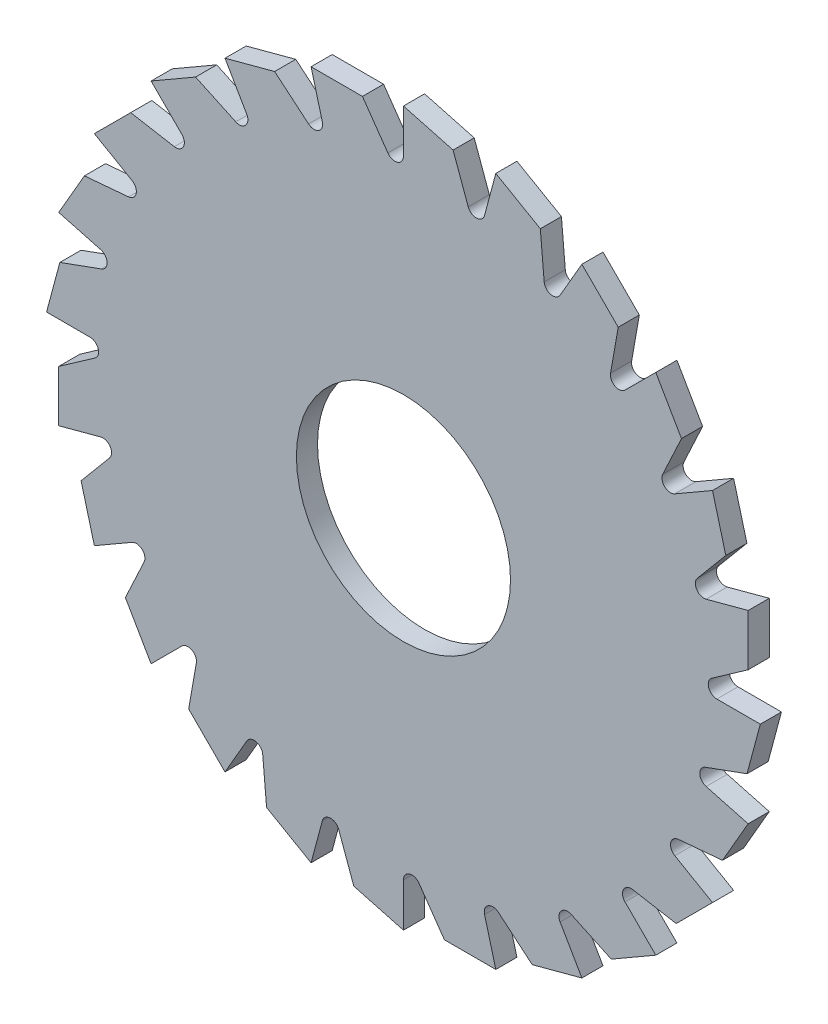
SolidWorks part; units mm, degrees
ref_plane "Front Plane" through (0, 0, 0) normal (0, 0, 1) x (1, 0, 0)
ref_plane "Top Plane" through (0, 0, 0) normal (0, 1, 0) x (1, 0, 0)
ref_plane "Right Plane" through (0, 0, 0) normal (1, 0, 0) x (0, 0, -1)
sketch "Sketch1" plane through (0, 0, 0) normal (0, 0, 1) x (1, 0, 0)
  line L0 (0, 31.75) -> (4.4162, 30.5667)
  line L1 (4.4162, 30.5667) -> (5.7634, 26.8652)
  line L2 (7.2155, 26.9286) -> (8.2175, 30.6681)
  line L3 (0, 31.75) -> (0, 0) construction
  line L4 (0, 0) -> (8.2175, 30.6681) construction
  line L5 (0, 31.75) -> (12.0811, 31.75) construction
  line L6 (6.3024, 26.3847) -> (0, 0) construction
  line L7 (6.3024, 26.3847) -> (4.0698, 26.918) construction
  line L8 (13.9393, 24.1436) -> (15.875, 27.4963)
  line L9 (12.177, 28.3821) -> (12.5203, 24.4581)
  line L10 (8.2175, 30.6681) -> (12.177, 28.3821)
  line L11 (19.7131, 19.7131) -> (22.4506, 22.4506)
  line L12 (19.1079, 24.2634) -> (18.4239, 20.3843)
  line L13 (15.875, 27.4963) -> (19.1079, 24.2634)
  line L14 (24.1436, 13.9393) -> (27.4963, 15.875)
  line L15 (24.7366, 18.4912) -> (23.072, 14.9212)
  line L16 (22.4506, 22.4506) -> (24.7366, 18.4912)
  line L17 (26.9286, 7.2155) -> (30.6681, 8.2175)
  line L18 (28.6796, 11.4588) -> (26.1477, 8.4413)
  line L19 (27.4963, 15.875) -> (28.6796, 11.4588)
  line L20 (27.8786, 0) -> (31.75, 0)
  line L21 (30.6681, 3.6455) -> (27.4415, 1.3862)
  line L22 (30.6681, 8.2175) -> (30.6681, 3.6455)
  line L23 (26.9286, -7.2155) -> (30.6681, -8.2175)
  line L24 (30.5667, -4.4162) -> (26.8652, -5.7634)
  line L25 (31.75, 0) -> (30.5667, -4.4162)
  line L26 (24.1436, -13.9393) -> (27.4963, -15.875)
  line L27 (28.3821, -12.177) -> (24.4581, -12.5203)
  line L28 (30.6681, -8.2175) -> (28.3821, -12.177)
  line L29 (19.7131, -19.7131) -> (22.4506, -22.4506)
  line L30 (24.2634, -19.1079) -> (20.3843, -18.4239)
  line L31 (27.4963, -15.875) -> (24.2634, -19.1079)
  line L32 (13.9393, -24.1436) -> (15.875, -27.4963)
  line L33 (18.4912, -24.7366) -> (14.9212, -23.072)
  line L34 (22.4506, -22.4506) -> (18.4912, -24.7366)
  line L35 (7.2155, -26.9286) -> (8.2175, -30.6681)
  line L36 (11.4588, -28.6796) -> (8.4413, -26.1477)
  line L37 (15.875, -27.4963) -> (11.4588, -28.6796)
  line L38 (0, -27.8786) -> (0, -31.75)
  line L39 (3.6455, -30.6681) -> (1.3862, -27.4415)
  line L40 (8.2175, -30.6681) -> (3.6455, -30.6681)
  line L41 (-7.2155, -26.9286) -> (-8.2175, -30.6681)
  line L42 (-4.4162, -30.5667) -> (-5.7634, -26.8652)
  line L43 (0, -31.75) -> (-4.4162, -30.5667)
  line L44 (-13.9393, -24.1436) -> (-15.875, -27.4963)
  line L45 (-12.177, -28.3821) -> (-12.5203, -24.4581)
  line L46 (-8.2175, -30.6681) -> (-12.177, -28.3821)
  line L47 (-19.7131, -19.7131) -> (-22.4506, -22.4506)
  line L48 (-19.1079, -24.2634) -> (-18.4239, -20.3843)
  line L49 (-15.875, -27.4963) -> (-19.1079, -24.2634)
  line L50 (-24.1436, -13.9393) -> (-27.4963, -15.875)
  line L51 (-24.7366, -18.4912) -> (-23.072, -14.9212)
  line L52 (-22.4506, -22.4506) -> (-24.7366, -18.4912)
  line L53 (-26.9286, -7.2155) -> (-30.6681, -8.2175)
  line L54 (-28.6796, -11.4588) -> (-26.1477, -8.4413)
  line L55 (-27.4963, -15.875) -> (-28.6796, -11.4588)
  line L56 (-27.8786, 0) -> (-31.75, 0)
  line L57 (-30.6681, -3.6455) -> (-27.4415, -1.3862)
  line L58 (-30.6681, -8.2175) -> (-30.6681, -3.6455)
  line L59 (-26.9286, 7.2155) -> (-30.6681, 8.2175)
  line L60 (-30.5667, 4.4162) -> (-26.8652, 5.7634)
  line L61 (-31.75, 0) -> (-30.5667, 4.4162)
  line L62 (-24.1436, 13.9393) -> (-27.4963, 15.875)
  line L63 (-28.3821, 12.177) -> (-24.4581, 12.5203)
  line L64 (-30.6681, 8.2175) -> (-28.3821, 12.177)
  line L65 (-19.7131, 19.7131) -> (-22.4506, 22.4506)
  line L66 (-24.2634, 19.1079) -> (-20.3843, 18.4239)
  line L67 (-27.4963, 15.875) -> (-24.2634, 19.1079)
  line L68 (-13.9393, 24.1436) -> (-15.875, 27.4963)
  line L69 (-18.4912, 24.7366) -> (-14.9212, 23.072)
  line L70 (-22.4506, 22.4506) -> (-18.4912, 24.7366)
  line L71 (-7.2155, 26.9286) -> (-8.2175, 30.6681)
  line L72 (-11.4588, 28.6796) -> (-8.4413, 26.1477)
  line L73 (-15.875, 27.4963) -> (-11.4588, 28.6796)
  line L74 (0, 27.8786) -> (0, 31.75)
  line L75 (-3.6455, 30.6681) -> (-1.3862, 27.4415)
  line L76 (-8.2175, 30.6681) -> (-3.6455, 30.6681)
  circle A0 centre (0, 0) radius 31.75 construction
  circle A1 centre (0, 0) radius 9.525
  circle A2 centre (0, 0) radius 27.127 construction
  arc A3 (5.7634, 26.8652) -> (7.2155, 26.9286) centre (6.4795, 27.1259) ccw
  arc A4 (12.5203, 24.4581) -> (13.9393, 24.1436) centre (13.2794, 24.5246) ccw
  arc A5 (18.4239, 20.3843) -> (19.7131, 19.7131) centre (19.1743, 20.2519) ccw
  arc A6 (23.072, 14.9212) -> (24.1436, 13.9393) centre (23.7626, 14.5992) ccw
  arc A7 (26.1477, 8.4413) -> (26.9286, 7.2155) centre (26.7314, 7.9515) ccw
  arc A8 (27.4415, 1.3862) -> (27.8786, 0) centre (27.8786, 0.762) ccw
  arc A9 (26.8652, -5.7634) -> (26.9286, -7.2155) centre (27.1259, -6.4795) ccw
  arc A10 (24.4581, -12.5203) -> (24.1436, -13.9393) centre (24.5246, -13.2794) ccw
  arc A11 (20.3843, -18.4239) -> (19.7131, -19.7131) centre (20.2519, -19.1743) ccw
  arc A12 (14.9212, -23.072) -> (13.9393, -24.1436) centre (14.5992, -23.7626) ccw
  arc A13 (8.4413, -26.1477) -> (7.2155, -26.9286) centre (7.9515, -26.7314) ccw
  arc A14 (1.3862, -27.4415) -> (0, -27.8786) centre (0.762, -27.8786) ccw
  arc A15 (-5.7634, -26.8652) -> (-7.2155, -26.9286) centre (-6.4795, -27.1259) ccw
  arc A16 (-12.5203, -24.4581) -> (-13.9393, -24.1436) centre (-13.2794, -24.5246) ccw
  arc A17 (-18.4239, -20.3843) -> (-19.7131, -19.7131) centre (-19.1743, -20.2519) ccw
  arc A18 (-23.072, -14.9212) -> (-24.1436, -13.9393) centre (-23.7626, -14.5992) ccw
  arc A19 (-26.1477, -8.4413) -> (-26.9286, -7.2155) centre (-26.7314, -7.9515) ccw
  arc A20 (-27.4415, -1.3862) -> (-27.8786, 0) centre (-27.8786, -0.762) ccw
  arc A21 (-26.8652, 5.7634) -> (-26.9286, 7.2155) centre (-27.1259, 6.4795) ccw
  arc A22 (-24.4581, 12.5203) -> (-24.1436, 13.9393) centre (-24.5246, 13.2794) ccw
  arc A23 (-20.3843, 18.4239) -> (-19.7131, 19.7131) centre (-20.2519, 19.1743) ccw
  arc A24 (-14.9212, 23.072) -> (-13.9393, 24.1436) centre (-14.5992, 23.7626) ccw
  arc A25 (-8.4413, 26.1477) -> (-7.2155, 26.9286) centre (-7.9515, 26.7314) ccw
  arc A26 (-1.3862, 27.4415) -> (0, 27.8786) centre (-0.762, 27.8786) ccw
  dimension "D1" = 63.5
  dimension "D2" = 19.05
  dimension "D3" = 125
  dimension "D7" = 0.762
  dimension "D4" = 15
  dimension "D5" = 15
  dimension "D6" = 4.572
  dimension "D8" = 24
extrude "Boss-Extrude1" add sketch "Sketch1" along normal blind 1.8796 contours A26 L75 L76 L71 A25 L72 L73 L68 A24 L69 L70 L65 A23 L66 L67 L62 A22 L63 L64 L59 A21 L60 L61 L56 A20 L57 L58 L53 A19 L54 L55 L50 A18 L51 L52 L47 A17 L48 L49 L44 A16 L45 L46 L41 A15 L42 L43 L38 A14 L39 L40 region at (1.9757, 30.2909, 0)
ref_plane "Plane1" through (0, 0, 0.9398) normal (0, 0, 1) x (1, 0, 0)
sketch "Sketch2" plane through (0, 0, 0) normal (0, 0, 1) x (1, 0, 0)
  line L0 (31.75, -31.75) -> (31.75, 31.75)
  line L1 (400.05, -31.75) -> (-31.75, -31.75)
  line L2 (400.05, -31.75) -> (400.05, 400.05)
  line L3 (400.05, 400.05) -> (-31.75, 400.05)
  line L4 (-31.75, -31.75) -> (-31.75, 400.05)
  line L5 (184.15, 400.05) -> (184.15, -31.75) construction
  line L6 (400.05, 184.15) -> (-31.75, 184.15) construction
  line L7 (-31.75, -31.75) -> (31.75, -31.75)
  line L8 (-31.75, -31.75) -> (-31.75, 31.75)
  line L9 (-31.75, 31.75) -> (31.75, 31.75)
  line L10 (31.75, -31.75) -> (31.75, 31.75)
  line L11 (0, 31.75) -> (0, -31.75) construction
  line L12 (-31.75, 0) -> (31.75, 0) construction
  line L13 (31.75, -31.75) -> (95.25, -31.75)
  line L14 (95.25, -31.75) -> (95.25, 31.75)
  line L15 (31.75, 31.75) -> (95.25, 31.75)
  line L16 (95.25, -31.75) -> (95.25, 31.75)
  line L17 (95.25, -31.75) -> (158.75, -31.75)
  line L18 (158.75, -31.75) -> (158.75, 31.75)
  line L19 (95.25, 31.75) -> (158.75, 31.75)
  line L20 (158.75, -31.75) -> (158.75, 31.75)
  line L21 (158.75, -31.75) -> (222.25, -31.75)
  line L22 (222.25, -31.75) -> (222.25, 31.75)
  line L23 (158.75, 31.75) -> (222.25, 31.75)
  line L24 (222.25, -31.75) -> (222.25, 31.75)
  line L25 (222.25, -31.75) -> (285.75, -31.75)
  line L26 (285.75, -31.75) -> (285.75, 31.75)
  line L27 (222.25, 31.75) -> (285.75, 31.75)
  line L28 (285.75, -31.75) -> (285.75, 31.75)
  line L29 (285.75, -31.75) -> (349.25, -31.75)
  line L30 (349.25, -31.75) -> (349.25, 31.75)
  line L31 (285.75, 31.75) -> (349.25, 31.75)
  line L32 (31.75, 31.75) -> (31.75, 95.25)
  line L33 (31.75, 31.75) -> (95.25, 31.75)
  line L34 (95.25, 31.75) -> (95.25, 95.25)
  line L35 (31.75, 95.25) -> (95.25, 95.25)
  line L36 (95.25, 31.75) -> (95.25, 95.25)
  line L37 (95.25, 31.75) -> (158.75, 31.75)
  line L38 (158.75, 31.75) -> (158.75, 95.25)
  line L39 (95.25, 95.25) -> (158.75, 95.25)
  line L40 (158.75, 31.75) -> (158.75, 95.25)
  line L41 (158.75, 31.75) -> (222.25, 31.75)
  line L42 (222.25, 31.75) -> (222.25, 95.25)
  line L43 (158.75, 95.25) -> (222.25, 95.25)
  line L44 (222.25, 31.75) -> (222.25, 95.25)
  line L45 (222.25, 31.75) -> (285.75, 31.75)
  line L46 (285.75, 31.75) -> (285.75, 95.25)
  line L47 (222.25, 95.25) -> (285.75, 95.25)
  line L48 (285.75, 31.75) -> (285.75, 95.25)
  line L49 (285.75, 31.75) -> (349.25, 31.75)
  line L50 (349.25, 31.75) -> (349.25, 95.25)
  line L51 (285.75, 95.25) -> (349.25, 95.25)
  line L52 (31.75, 95.25) -> (31.75, 158.75)
  line L53 (31.75, 95.25) -> (95.25, 95.25)
  line L54 (95.25, 95.25) -> (95.25, 158.75)
  line L55 (31.75, 158.75) -> (95.25, 158.75)
  line L56 (95.25, 95.25) -> (95.25, 158.75)
  line L57 (95.25, 95.25) -> (158.75, 95.25)
  line L58 (158.75, 95.25) -> (158.75, 158.75)
  line L59 (95.25, 158.75) -> (158.75, 158.75)
  line L60 (158.75, 95.25) -> (158.75, 158.75)
  line L61 (158.75, 95.25) -> (222.25, 95.25)
  line L62 (222.25, 95.25) -> (222.25, 158.75)
  line L63 (158.75, 158.75) -> (222.25, 158.75)
  line L64 (222.25, 95.25) -> (222.25, 158.75)
  line L65 (222.25, 95.25) -> (285.75, 95.25)
  line L66 (285.75, 95.25) -> (285.75, 158.75)
  line L67 (222.25, 158.75) -> (285.75, 158.75)
  line L68 (285.75, 95.25) -> (285.75, 158.75)
  line L69 (285.75, 95.25) -> (349.25, 95.25)
  line L70 (349.25, 95.25) -> (349.25, 158.75)
  line L71 (285.75, 158.75) -> (349.25, 158.75)
  line L72 (31.75, 158.75) -> (31.75, 222.25)
  line L73 (31.75, 158.75) -> (95.25, 158.75)
  line L74 (95.25, 158.75) -> (95.25, 222.25)
  line L75 (31.75, 222.25) -> (95.25, 222.25)
  line L76 (95.25, 158.75) -> (95.25, 222.25)
  line L77 (95.25, 158.75) -> (158.75, 158.75)
  line L78 (158.75, 158.75) -> (158.75, 222.25)
  line L79 (95.25, 222.25) -> (158.75, 222.25)
  line L80 (158.75, 158.75) -> (158.75, 222.25)
  line L81 (158.75, 158.75) -> (222.25, 158.75)
  line L82 (222.25, 158.75) -> (222.25, 222.25)
  line L83 (158.75, 222.25) -> (222.25, 222.25)
  line L84 (222.25, 158.75) -> (222.25, 222.25)
  line L85 (222.25, 158.75) -> (285.75, 158.75)
  line L86 (285.75, 158.75) -> (285.75, 222.25)
  line L87 (222.25, 222.25) -> (285.75, 222.25)
  line L88 (285.75, 158.75) -> (285.75, 222.25)
  line L89 (285.75, 158.75) -> (349.25, 158.75)
  line L90 (349.25, 158.75) -> (349.25, 222.25)
  line L91 (285.75, 222.25) -> (349.25, 222.25)
  line L92 (31.75, 222.25) -> (31.75, 285.75)
  line L93 (31.75, 222.25) -> (95.25, 222.25)
  line L94 (95.25, 222.25) -> (95.25, 285.75)
  line L95 (31.75, 285.75) -> (95.25, 285.75)
  line L96 (95.25, 222.25) -> (95.25, 285.75)
  line L97 (95.25, 222.25) -> (158.75, 222.25)
  line L98 (158.75, 222.25) -> (158.75, 285.75)
  line L99 (95.25, 285.75) -> (158.75, 285.75)
  line L100 (158.75, 222.25) -> (158.75, 285.75)
  line L101 (158.75, 222.25) -> (222.25, 222.25)
  line L102 (222.25, 222.25) -> (222.25, 285.75)
  line L103 (158.75, 285.75) -> (222.25, 285.75)
  line L104 (222.25, 222.25) -> (222.25, 285.75)
  line L105 (222.25, 222.25) -> (285.75, 222.25)
  line L106 (285.75, 222.25) -> (285.75, 285.75)
  line L107 (222.25, 285.75) -> (285.75, 285.75)
  line L108 (285.75, 222.25) -> (285.75, 285.75)
  line L109 (285.75, 222.25) -> (349.25, 222.25)
  line L110 (349.25, 222.25) -> (349.25, 285.75)
  line L111 (285.75, 285.75) -> (349.25, 285.75)
  line L112 (31.75, 285.75) -> (31.75, 349.25)
  line L113 (31.75, 285.75) -> (95.25, 285.75)
  line L114 (95.25, 285.75) -> (95.25, 349.25)
  line L115 (31.75, 349.25) -> (95.25, 349.25)
  line L116 (95.25, 285.75) -> (95.25, 349.25)
  line L117 (95.25, 285.75) -> (158.75, 285.75)
  line L118 (158.75, 285.75) -> (158.75, 349.25)
  line L119 (95.25, 349.25) -> (158.75, 349.25)
  line L120 (158.75, 285.75) -> (158.75, 349.25)
  line L121 (158.75, 285.75) -> (222.25, 285.75)
  line L122 (222.25, 285.75) -> (222.25, 349.25)
  line L123 (158.75, 349.25) -> (222.25, 349.25)
  line L124 (222.25, 285.75) -> (222.25, 349.25)
  line L125 (222.25, 285.75) -> (285.75, 285.75)
  line L126 (285.75, 285.75) -> (285.75, 349.25)
  line L127 (222.25, 349.25) -> (285.75, 349.25)
  line L128 (285.75, 285.75) -> (285.75, 349.25)
  line L129 (285.75, 285.75) -> (349.25, 285.75)
  line L130 (349.25, 285.75) -> (349.25, 349.25)
  line L131 (285.75, 349.25) -> (349.25, 349.25)
  line L132 (-31.75, 31.75) -> (-31.75, 95.25)
  line L133 (-31.75, 31.75) -> (31.75, 31.75)
  line L134 (31.75, 31.75) -> (31.75, 95.25)
  line L135 (-31.75, 95.25) -> (31.75, 95.25)
  line L136 (-31.75, 95.25) -> (-31.75, 158.75)
  line L137 (-31.75, 95.25) -> (31.75, 95.25)
  line L138 (31.75, 95.25) -> (31.75, 158.75)
  line L139 (-31.75, 158.75) -> (31.75, 158.75)
  line L140 (-31.75, 158.75) -> (-31.75, 222.25)
  line L141 (-31.75, 158.75) -> (31.75, 158.75)
  line L142 (31.75, 158.75) -> (31.75, 222.25)
  line L143 (-31.75, 222.25) -> (31.75, 222.25)
  line L144 (-31.75, 222.25) -> (-31.75, 285.75)
  line L145 (-31.75, 222.25) -> (31.75, 222.25)
  line L146 (31.75, 222.25) -> (31.75, 285.75)
  line L147 (-31.75, 285.75) -> (31.75, 285.75)
  line L148 (-31.75, 285.75) -> (-31.75, 349.25)
  line L149 (-31.75, 285.75) -> (31.75, 285.75)
  line L150 (31.75, 285.75) -> (31.75, 349.25)
  line L151 (-31.75, 349.25) -> (31.75, 349.25)
  line L152 (-31.75, -31.75) -> (31.75, -31.75) construction
  line L153 (-31.75, -31.75) -> (-31.75, 31.75) construction
  point P0 (184.15, 184.15)
  point P4 (0, 0)
  dimension "D1" = 431.8
  dimension "D2" = 431.8
  dimension "D3" = 63.5
  dimension "D4" = 6
  dimension "D6" = 63.5
  dimension "D7" = 63.5
  dimension "D5" = 6
